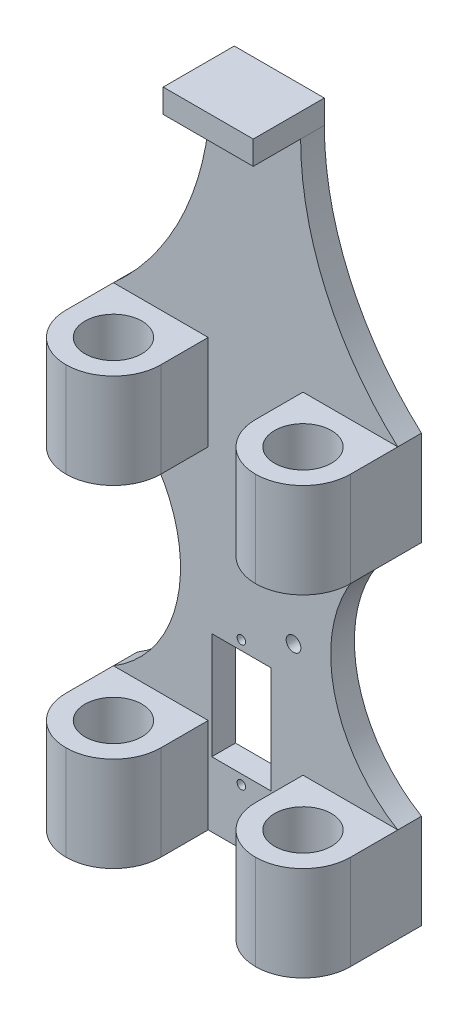
SolidWorks part; units mm, degrees
ref_plane "Спереди" through (0, 0, 0) normal (0, 0, 1) x (1, 0, 0)
ref_plane "Сверху" through (0, 0, 0) normal (0, 1, 0) x (1, 0, 0)
ref_plane "Справа" through (0, 0, 0) normal (1, 0, 0) x (0, 0, -1)
other "Configuration Table"
sketch "Sketch1" plane through (0, 0, 0) normal (0, 0, 1) x (1, 0, 0)
  line L0 (8, -2) -> (8, -38) construction
  line L1 (30, -45) -> (-30, -45)
  line L2 (30, -45) -> (30, 45)
  line L3 (30, 45) -> (-30, 45)
  line L4 (-30, -45) -> (-30, 45)
  line L5 (-3, 45) -> (-3, -45) construction
  line L6 (30, 0) -> (-30, 0) construction
  line L7 (-9.25, -8.75) -> (3.25, -8.75)
  line L8 (-9.25, -8.75) -> (-9.25, -31.25)
  line L9 (-9.25, -31.25) -> (3.25, -31.25)
  line L10 (3.25, -8.75) -> (3.25, -31.25)
  line L11 (-3, -31.25) -> (-3, -8.75) construction
  line L12 (-9.25, -20) -> (3.25, -20) construction
  circle A0 centre (-3, -33.25) radius 0.9
  circle A1 centre (-3, -6.75) radius 0.9
  circle A2 centre (8, -38) radius 1.55
  circle A3 centre (8, -2) radius 1.55
  point P0 (0, 0)
  point P4 (-3, -20)
  point P16 (8, -20)
  dimension "D8" = 1.8
  dimension "D10" = 3.1
  dimension "D2" = 90
  dimension "D3" = 22.5
  dimension "D4" = 12.5
  dimension "D5" = 25
  dimension "D6" = 2
  dimension "D7" = 2
  dimension "D9" = 36
  dimension "D11" = 33
  dimension "D12" = 11
  dimension "D13" = 60
extrude "Boss-Extrude1" add sketch "Sketch1" along normal blind 5
sketch "Sketch2" plane through (0, 0, 5) normal (0, 0, 1) x (1, 0, 0)
  line L1 (-30, -45) -> (-10, -45)
  line L2 (-30, -45) -> (-30, -25)
  line L3 (-30, -25) -> (-10, -25)
  line L4 (-10, -45) -> (-10, -25)
  line L5 (-30, 45) -> (-10, 45)
  line L6 (-30, 45) -> (-30, 25)
  line L7 (-30, 25) -> (-10, 25)
  line L8 (-10, 45) -> (-10, 25)
  line L9 (30, 45) -> (10, 45)
  line L10 (30, 45) -> (30, 25)
  line L11 (30, 25) -> (10, 25)
  line L12 (10, 45) -> (10, 25)
  line L13 (30, -45) -> (10, -45)
  line L14 (30, -45) -> (30, -25)
  line L15 (30, -25) -> (10, -25)
  line L16 (10, -45) -> (10, -25)
  dimension "D1" = 20
extrude "Boss-Extrude2" add sketch "Sketch2" along normal blind 20
fillet "Fillet1" radius 10 8 edges at (10, -35, 25) (30, -35, 25) (30, 35, 25) (10, 35, 25) (-30, 35, 25) (-10, 35, 25) (-10, -35, 25) (-30, -35, 25)
sketch "Sketch3" plane through (0, -45, 0) normal (0, -1, 0) x (1, 0, 0)
  line L0 (-20, 25) -> (-20, 0) construction
  line L1 (-30, 0) -> (30, 0) construction
  line L2 (20, 25) -> (20, 0) construction
  circle A0 centre (-20, 15) radius 6
  circle A1 centre (20, 15) radius 6
  arc A2 (-20, 25) -> (-30, 15) centre (-20, 15) ccw construction
  arc A3 (20, 25) -> (10, 15) centre (20, 15) ccw construction
  dimension "D1" = 12
extrude "Cut-Extrude1" cut sketch "Sketch3" against normal through all
sketch "Sketch4" plane through (0, 0, 5) normal (0, 0, 1) x (1, 0, 0)
  line L0 (-30, 25) -> (-30, -25) construction
  line L1 (-30, 25) -> (-30, -25)
  line L2 (30, 25) -> (30, -25)
  arc A0 (-30, 25) -> (-30, -25) centre (-45, 0) cw
  arc A1 (30, 25) -> (30, -25) centre (45, 0) ccw
  point P12 (-30, 0)
  dimension "D1" = 15
extrude "Cut-Extrude2" cut sketch "Sketch4" against normal up to next
sketch "Sketch5" plane through (0, 45, 0) normal (0, 1, 0) x (1, 0, 0)
  line L0 (30, -15) -> (30, 0) construction
  line L1 (-30, 0) -> (30, 0)
  line L2 (-30, 0) -> (-30, -5)
  line L3 (-30, -5) -> (30, -5)
  line L4 (30, 0) -> (30, -5)
  line L5 (10, -5) -> (-10, -5) construction
extrude "Boss-Extrude3" add sketch "Sketch5" along normal blind 51
sketch "Sketch6" plane through (0, 0, 5) normal (0, 0, 1) x (1, 0, 0)
  line L0 (-30, 96) -> (30, 96) construction
  line L1 (-9.5, 91) -> (9.5, 91) construction
  line L2 (-9.5, 91) -> (-9.5, 96)
  line L3 (-9.5, 96) -> (9.5, 96) construction
  line L4 (9.5, 91) -> (9.5, 96)
  line L5 (0, 96) -> (0, 91) construction
  line L6 (-9.5, 93.5) -> (9.5, 93.5) construction
  line L7 (-9.5, 96) -> (-30, 96)
  line L8 (-30, 96) -> (-30, 45)
  line L9 (9.5, 96) -> (30, 96)
  line L10 (30, 96) -> (30, 45)
  arc A0 (-9.5, 91) -> (-30, 45) centre (-71.3598, 91) cw
  arc A1 (9.5, 91) -> (30, 45) centre (71.3598, 91) ccw
  point P0 (0, 93.5)
  point P6 (0, 96)
  dimension "D1" = 5
  dimension "D2" = 19
extrude "Cut-Extrude3" cut sketch "Sketch6" against normal up to next
sketch "Sketch7" plane through (0, 0, 5) normal (0, 0, 1) x (1, 0, 0)
  line L1 (-9.5, 96) -> (9.5, 96)
  line L2 (-9.5, 96) -> (-9.5, 91)
  line L3 (-9.5, 91) -> (9.5, 91)
  line L4 (9.5, 96) -> (9.5, 91)
extrude "Boss-Extrude4" add sketch "Sketch7" along normal blind 10
